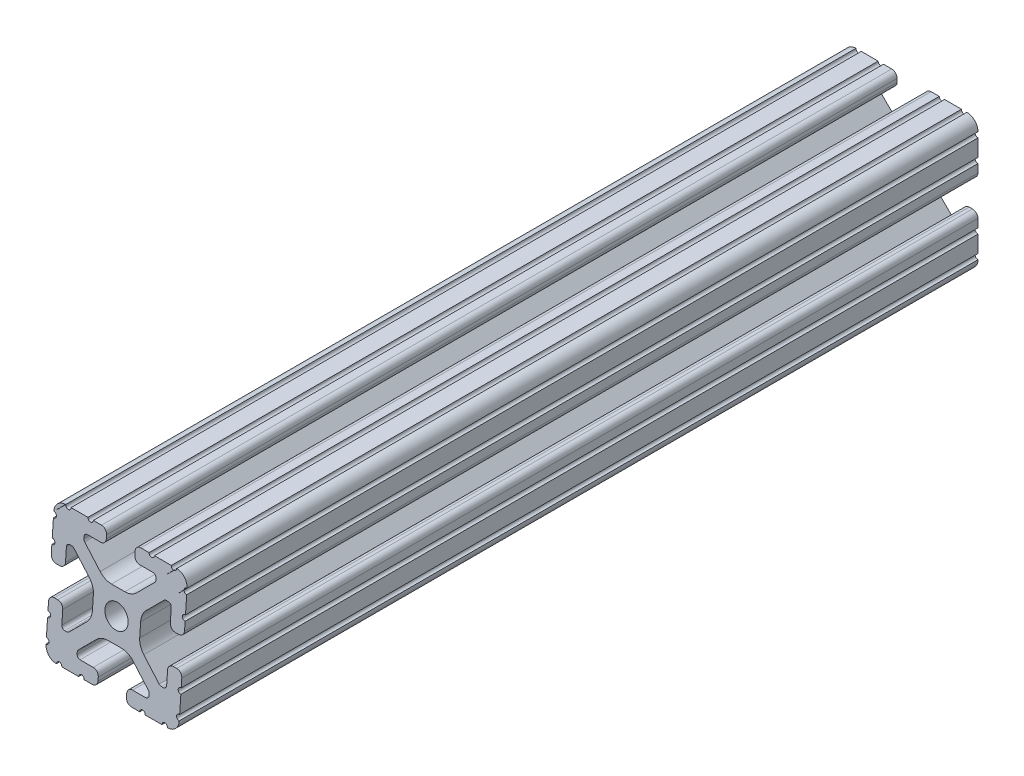
SolidWorks part; units mm, degrees
material "6061 Alloy"
ref_plane "Front Plane" through (0, 0, 0) normal (0, 0, 1) x (1, 0, 0)
ref_plane "Top Plane" through (0, 0, 0) normal (0, 1, 0) x (1, 0, 0)
ref_plane "Right Plane" through (0, 0, 0) normal (1, 0, 0) x (0, 0, -1)
sketch "Sketch1" plane through (0, 0, 0) normal (0, 0, 1) x (1, 0, 0)
  line L0 (0, 25.6181) -> (0, -24.623) construction
  line L1 (-20.8943, 0) -> (20.4607, 0) construction
  line L2 (-10.0229, 12.9148) -> (-5.2522, 8.144)
  line L3 (-10.287, 14.0843) -> (-10.287, 13.5524)
  line L4 (-5.6176, 14.986) -> (-9.3853, 14.986)
  line L5 (-4.064, 17.4964) -> (-4.064, 16.5396)
  line L6 (-7.9742, 19.05) -> (-5.6176, 19.05)
  line L7 (-14.3277, 19.05) -> (-9.4982, 19.05)
  line L8 (-19.05, 9.4961) -> (-19.05, 14.3277)
  line L9 (-19.05, 5.6176) -> (-19.05, 7.9763)
  line L10 (-16.5396, 4.064) -> (-17.4964, 4.064)
  line L11 (-14.986, 9.3853) -> (-14.986, 5.6176)
  line L12 (-13.516, 10.287) -> (-14.0843, 10.287)
  line L13 (-8.1476, 5.2921) -> (-12.8784, 10.0229)
  line L14 (-6.7564, -1.9335) -> (-6.7564, 1.9335)
  line L15 (-12.8784, -10.0229) -> (-8.1476, -5.2921)
  line L16 (-14.0843, -10.287) -> (-13.516, -10.287)
  line L17 (-14.986, -5.6176) -> (-14.986, -9.3853)
  line L18 (-17.4964, -4.064) -> (-16.5396, -4.064)
  line L19 (-19.05, -7.9763) -> (-19.05, -5.6176)
  line L20 (-19.05, -14.3277) -> (-19.05, -9.4961)
  line L21 (-9.4961, -19.05) -> (-14.3277, -19.05)
  line L22 (-5.6176, -19.05) -> (-7.9763, -19.05)
  line L23 (-4.064, -17.4964) -> (-4.064, -16.5396)
  line L24 (10.0229, -12.9148) -> (5.2522, -8.144)
  line L25 (10.287, -14.0843) -> (10.287, -13.5524)
  line L26 (5.6176, -14.986) -> (9.3853, -14.986)
  line L28 (-1.9022, 6.7564) -> (1.9022, 6.7564)
  line L29 (-1.9022, -6.7564) -> (1.9022, -6.7564)
  line L31 (-5.6176, -14.986) -> (-9.3853, -14.986)
  line L32 (-10.287, -14.0843) -> (-10.287, -13.5524)
  line L33 (-10.0229, -12.9148) -> (-5.2522, -8.144)
  line L66 (4.064, -16.5396) -> (4.064, -17.4964)
  line L67 (5.6176, -19.05) -> (7.9763, -19.05)
  line L68 (9.4961, -19.05) -> (14.3277, -19.05)
  line L69 (19.05, -14.3277) -> (19.05, -9.4961)
  line L70 (19.05, -7.9763) -> (19.05, -5.6176)
  line L71 (17.4964, -4.064) -> (16.5396, -4.064)
  line L72 (14.986, -5.6176) -> (14.986, -9.3853)
  line L73 (14.0843, -10.287) -> (13.516, -10.287)
  line L74 (12.8784, -10.0229) -> (8.1476, -5.2921)
  line L75 (6.7564, -1.9335) -> (6.7564, 1.9335)
  line L76 (8.1476, 5.2921) -> (12.8784, 10.0229)
  line L77 (13.516, 10.287) -> (14.0843, 10.287)
  line L78 (14.986, 9.3853) -> (14.986, 5.6176)
  line L79 (16.5396, 4.064) -> (17.4964, 4.064)
  line L80 (19.05, 5.6176) -> (19.05, 7.9763)
  line L81 (19.05, 9.4961) -> (19.05, 14.3277)
  line L82 (14.3277, 19.05) -> (9.4982, 19.05)
  line L83 (7.9742, 19.05) -> (5.6176, 19.05)
  line L84 (4.064, 17.4964) -> (4.064, 16.5396)
  line L85 (5.6176, 14.986) -> (9.3853, 14.986)
  line L86 (10.287, 14.0843) -> (10.287, 13.5524)
  line L87 (10.0229, 12.9148) -> (5.2522, 8.144)
  arc A0 (-10.0229, 12.9148) -> (-10.287, 13.5524) centre (-9.3853, 13.5524) cw
  circle A1 centre (0, 0) radius 3.3274
  arc A2 (-10.287, 14.0843) -> (-9.3853, 14.986) centre (-9.3853, 14.0843) cw
  arc A3 (-4.064, 16.5396) -> (-5.6176, 14.986) centre (-5.6176, 16.5396) cw
  arc A4 (-5.6176, 19.05) -> (-4.064, 17.4964) centre (-5.6176, 17.4964) cw
  arc A5 (-7.9742, 19.05) -> (-9.4982, 19.05) centre (-8.7362, 19.05) cw
  arc A6 (-14.3277, 19.05) -> (-15.8475, 19.05) centre (-15.0876, 18.9933) cw
  arc A7 (-19.05, 15.8475) -> (-15.8475, 19.05) centre (-15.8751, 15.8751) cw
  arc A8 (-19.05, 15.8475) -> (-19.05, 14.3277) centre (-18.9933, 15.0876) cw
  arc A9 (-19.05, 9.4961) -> (-19.05, 7.9763) centre (-18.9933, 8.7362) cw
  arc A10 (-17.4964, 4.064) -> (-19.05, 5.6176) centre (-17.4964, 5.6176) cw
  arc A11 (-14.986, 5.6176) -> (-16.5396, 4.064) centre (-16.5396, 5.6176) cw
  arc A12 (-14.986, 9.3853) -> (-14.0843, 10.287) centre (-14.0843, 9.3853) cw
  arc A13 (-13.516, 10.287) -> (-12.8784, 10.0229) centre (-13.516, 9.3853) cw
  arc A14 (-8.1476, 5.2921) -> (-6.7564, 1.9335) centre (-11.5062, 1.9335) cw
  arc A15 (-6.7564, -1.9335) -> (-8.1476, -5.2921) centre (-11.5062, -1.9335) cw
  arc A16 (-12.8784, -10.0229) -> (-13.516, -10.287) centre (-13.516, -9.3853) cw
  arc A17 (-14.0843, -10.287) -> (-14.986, -9.3853) centre (-14.0843, -9.3853) cw
  arc A18 (-16.5396, -4.064) -> (-14.986, -5.6176) centre (-16.5396, -5.6176) cw
  arc A19 (-19.05, -5.6176) -> (-17.4964, -4.064) centre (-17.4964, -5.6176) cw
  arc A20 (-19.05, -7.9763) -> (-19.05, -9.4961) centre (-18.9933, -8.7362) cw
  arc A21 (-19.05, -14.3277) -> (-19.05, -15.8475) centre (-18.9933, -15.0876) cw
  arc A22 (-15.8475, -19.05) -> (-19.05, -15.8475) centre (-15.8751, -15.8751) cw
  arc A23 (-15.8475, -19.05) -> (-14.3277, -19.05) centre (-15.0876, -18.9933) cw
  arc A24 (-9.4961, -19.05) -> (-7.9763, -19.05) centre (-8.7362, -18.9933) cw
  arc A25 (-4.064, -17.4964) -> (-5.6176, -19.05) centre (-5.6176, -17.4964) cw
  arc A26 (-5.2522, -8.144) -> (-1.9022, -6.7564) centre (-1.9022, -11.494) cw
  arc A27 (1.9022, -6.7564) -> (5.2522, -8.144) centre (1.9022, -11.494) cw
  arc A28 (10.0229, -12.9148) -> (10.287, -13.5524) centre (9.3853, -13.5524) cw
  arc A29 (10.287, -14.0843) -> (9.3853, -14.986) centre (9.3853, -14.0843) cw
  arc A30 (4.064, -16.5396) -> (5.6176, -14.986) centre (5.6176, -16.5396) cw
  arc A31 (-4.064, -16.5396) -> (-5.6176, -14.986) centre (-5.6176, -16.5396) ccw
  arc A32 (-10.287, -14.0843) -> (-9.3853, -14.986) centre (-9.3853, -14.0843) ccw
  arc A33 (-10.0229, -12.9148) -> (-10.287, -13.5524) centre (-9.3853, -13.5524) ccw
  arc A79 (4.064, -17.4964) -> (5.6176, -19.05) centre (5.6176, -17.4964) ccw
  arc A80 (9.4961, -19.05) -> (7.9763, -19.05) centre (8.7362, -18.9933) ccw
  arc A81 (15.8475, -19.05) -> (14.3277, -19.05) centre (15.0876, -18.9933) ccw
  arc A82 (15.8475, -19.05) -> (19.05, -15.8475) centre (15.8751, -15.8751) ccw
  arc A83 (19.05, -14.3277) -> (19.05, -15.8475) centre (18.9933, -15.0876) ccw
  arc A84 (19.05, -7.9763) -> (19.05, -9.4961) centre (18.9933, -8.7362) ccw
  arc A85 (19.05, -5.6176) -> (17.4964, -4.064) centre (17.4964, -5.6176) ccw
  arc A86 (16.5396, -4.064) -> (14.986, -5.6176) centre (16.5396, -5.6176) ccw
  arc A87 (14.0843, -10.287) -> (14.986, -9.3853) centre (14.0843, -9.3853) ccw
  arc A88 (12.8784, -10.0229) -> (13.516, -10.287) centre (13.516, -9.3853) ccw
  arc A89 (6.7564, -1.9335) -> (8.1476, -5.2921) centre (11.5062, -1.9335) ccw
  arc A90 (8.1476, 5.2921) -> (6.7564, 1.9335) centre (11.5062, 1.9335) ccw
  arc A91 (13.516, 10.287) -> (12.8784, 10.0229) centre (13.516, 9.3853) ccw
  arc A92 (14.986, 9.3853) -> (14.0843, 10.287) centre (14.0843, 9.3853) ccw
  arc A93 (14.986, 5.6176) -> (16.5396, 4.064) centre (16.5396, 5.6176) ccw
  arc A94 (17.4964, 4.064) -> (19.05, 5.6176) centre (17.4964, 5.6176) ccw
  arc A95 (19.05, 9.4961) -> (19.05, 7.9763) centre (18.9933, 8.7362) ccw
  arc A96 (19.05, 15.8475) -> (19.05, 14.3277) centre (18.9933, 15.0876) ccw
  arc A97 (19.05, 15.8475) -> (15.8475, 19.05) centre (15.8751, 15.8751) ccw
  arc A98 (14.3277, 19.05) -> (15.8475, 19.05) centre (15.0876, 18.9933) ccw
  arc A99 (7.9742, 19.05) -> (9.4982, 19.05) centre (8.7362, 19.05) ccw
  arc A100 (5.6176, 19.05) -> (4.064, 17.4964) centre (5.6176, 17.4964) ccw
  arc A101 (4.064, 16.5396) -> (5.6176, 14.986) centre (5.6176, 16.5396) ccw
  arc A102 (10.287, 14.0843) -> (9.3853, 14.986) centre (9.3853, 14.0843) ccw
  arc A103 (10.0229, 12.9148) -> (10.287, 13.5524) centre (9.3853, 13.5524) ccw
  arc A104 (1.9022, 6.7564) -> (5.2522, 8.144) centre (1.9022, 11.494) ccw
  arc A105 (-5.2522, 8.144) -> (-1.9022, 6.7564) centre (-1.9022, 11.494) ccw
  dimension "D1" = 6.6548
  dimension "D2" = 19.05
  dimension "D3" = 38.1
  dimension "D4" = 20.574
  dimension "D5" = 13.5128
  dimension "D6" = 4.064
  dimension "D7" = 8.128
  dimension "D8" = 4.064
  dimension "D9" = 12.2936
extrude "Extrude1" add sketch "Sketch1" against normal blind 228.6
sketch "Sketch2" plane through (19.05, 0, 0) normal (1, 0, 0) x (0, 0, -1)
  line L0 (0, -19.05) -> (0, 19.05)
  line L1 (228.6, 19.05) -> (0, 19.05) construction
  line L2 (0, 19.05) -> (2.6642, 19.05)
  line L3 (2.6642, 19.05) -> (0, -19.05)
  dimension "D1" = 4
extrude "Cut-Extrude1" cut sketch "Sketch2" against normal offset from surface (127 mm away) 127 up to face at (19.05, 11.9119, -114.3)
